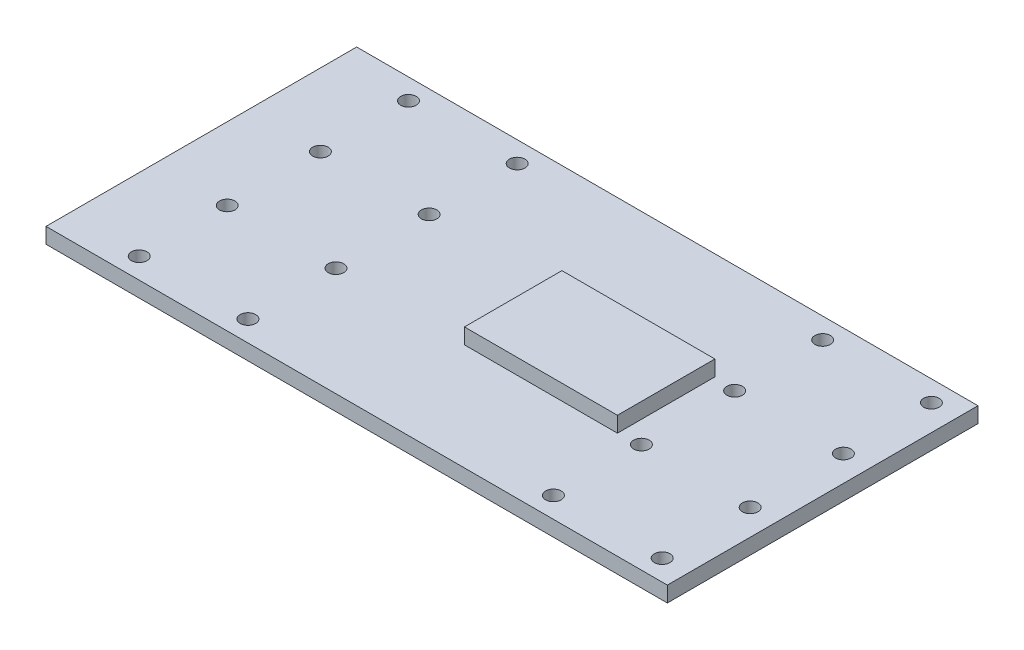
SolidWorks part; units mm, degrees
ref_plane "Front Plane" through (0, 0, 0) normal (0, 0, 1) x (1, 0, 0)
ref_plane "Top Plane" through (0, 0, 0) normal (0, 1, 0) x (1, 0, 0)
ref_plane "Right Plane" through (0, 0, 0) normal (1, 0, 0) x (0, 0, -1)
sketch "Sketch1" plane through (0, 0, 0) normal (0, 1, 0) x (1, 0, 0)
  line L1 (-60, -30) -> (60, -30)
  line L2 (-60, -30) -> (-60, 30)
  line L3 (-60, 30) -> (60, 30)
  line L4 (60, -30) -> (60, 30)
  line L5 (-60, -30) -> (60, 30) construction
  line L6 (-60, 30) -> (60, -30) construction
  line L7 (-46, 26) -> (-25, 26) construction
  line L8 (-46, 26) -> (-46, 9) construction
  line L9 (-46, 9) -> (-25, 9) construction
  line L10 (-25, 26) -> (-25, 9) construction
  line L11 (34, 26) -> (55, 26) construction
  line L12 (34, 26) -> (34, 9) construction
  line L13 (34, 9) -> (55, 9) construction
  line L14 (55, 26) -> (55, 9) construction
  line L15 (34, -9) -> (55, -9) construction
  line L16 (34, -9) -> (34, -26) construction
  line L17 (34, -26) -> (55, -26) construction
  line L18 (55, -9) -> (55, -26) construction
  line L19 (-46, -9) -> (-25, -9) construction
  line L20 (-46, -9) -> (-46, -26) construction
  line L21 (-46, -26) -> (-25, -26) construction
  line L22 (-25, -9) -> (-25, -26) construction
  line L23 (34, 9) -> (34, -9) construction
  circle A0 centre (-25, 26) radius 1.5
  circle A1 centre (-46, 26) radius 1.5
  circle A2 centre (-46, 9) radius 1.5
  circle A3 centre (-25, 9) radius 1.5
  circle A4 centre (-25, -9) radius 1.5
  circle A5 centre (-46, -9) radius 1.5
  circle A6 centre (-25, -26) radius 1.5
  circle A7 centre (-46, -26) radius 1.5
  circle A8 centre (55, 26) radius 1.5
  circle A9 centre (34, 26) radius 1.5
  circle A10 centre (34, -9) radius 1.5
  circle A11 centre (55, -9) radius 1.5
  circle A12 centre (55, -26) radius 1.5
  circle A13 centre (34, -26) radius 1.5
  circle A14 centre (55, 9) radius 1.5
  circle A15 centre (34, 9) radius 1.5
  point P0 (0, 0)
  point P36 (34, 0)
  dimension "D5" = 3
  dimension "D1" = 80
  dimension "D2" = 35
  dimension "D3" = 21
  dimension "D4" = 17
  dimension "D6" = 60
  dimension "D7" = 5
  dimension "D8" = 120
extrude "Boss-Extrude1" add sketch "Sketch1" along normal blind 3
sketch "Sketch2" plane through (0, 3, 0) normal (0, 1, 0) x (1, 0, 0)
  line L0 (60, -30) -> (60, 30) construction
  line L1 (0.2254, -9.4125) -> (29.7746, -9.4125)
  line L2 (0.2254, -9.4125) -> (0.2254, 9.4125)
  line L3 (0.2254, 9.4125) -> (29.7746, 9.4125)
  line L4 (29.7746, -9.4125) -> (29.7746, 9.4125)
  line L5 (0.2254, -9.4125) -> (29.7746, 9.4125) construction
  line L6 (0.2254, 9.4125) -> (29.7746, -9.4125) construction
  point P0 (15, 0)
  dimension "D1" = 45
extrude "Boss-Extrude2" add sketch "Sketch2" along normal blind 3
